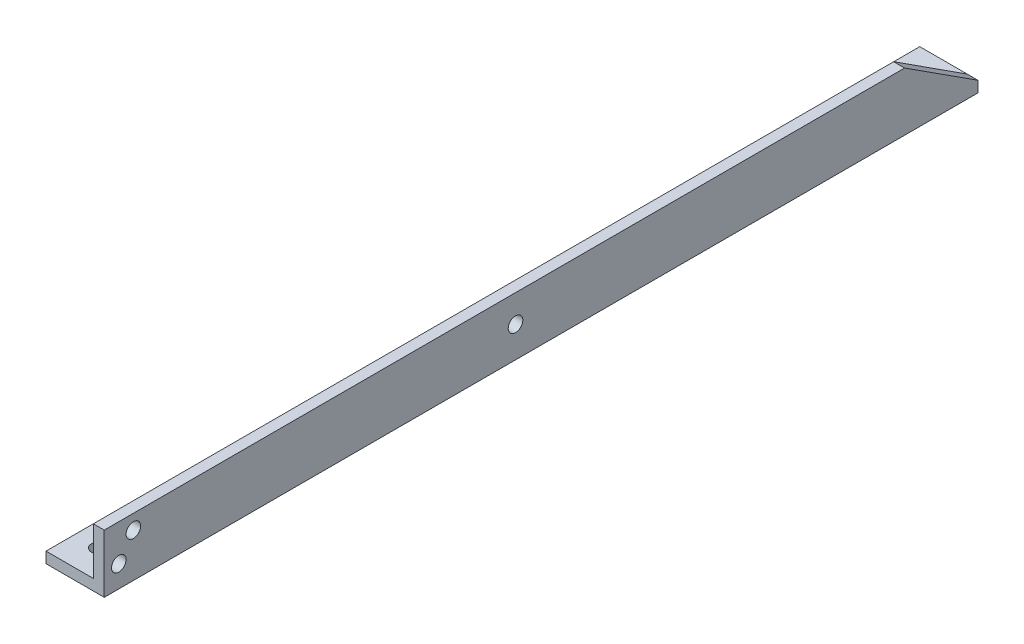
SolidWorks part; units mm, degrees
material "6061 Alloy"
ref_plane "Front Plane" through (0, 0, 0) normal (0, 0, 1) x (1, 0, 0)
ref_plane "Top Plane" through (0, 0, 0) normal (0, 1, 0) x (1, 0, 0)
ref_plane "Right Plane" through (0, 0, 0) normal (1, 0, 0) x (0, 0, -1)
sketch "Sketch1" plane through (0, 0, 0) normal (0, 0, 1) x (1, 0, 0)
  line L0 (0, 0) -> (0, -25.4)
  line L1 (0, -25.4) -> (-25.4, -25.4)
  line L2 (-25.4, -25.4) -> (-25.4, -20.6375)
  line L3 (-25.4, -20.6375) -> (-4.7625, -20.6375)
  line L4 (-4.7625, -20.6375) -> (-4.7625, 0)
  line L5 (-4.7625, 0) -> (0, 0)
  dimension "D1" = 4.7625
  dimension "D2" = 4.7625
  dimension "D3" = 25.4
  dimension "D4" = 25.4
extrude "Boss-Extrude1" add sketch "Sketch1" along normal blind 381
sketch "Sketch9" plane through (-4.7625, 0, 0) normal (-1, 0, 0) x (0, 0, 1)
  line L0 (0, -20.6375) -> (32.0266, 0)
  line L1 (381, 0) -> (0, 0) construction
  dimension "D1" = 38.1
extrude "Cut-Extrude2" cut sketch "Sketch9" against normal through all and the other way through all
sketch "Sketch10" plane through (-4.7625, 0, 0) normal (-1, 0, 0) x (0, 0, 1)
  line L0 (381, 0) -> (32.0266, 0) construction
  line L1 (381, 0) -> (381, -20.6375) construction
  circle A0 centre (374.65, -15.875) radius 3.175
  circle A1 centre (368.3, -6.35) radius 3.175
  dimension "D1" = 6.35
  dimension "D2" = 6.35
  dimension "D3" = 15.875
  dimension "D4" = 6.35
  dimension "D5" = 6.35
  dimension "D6" = 12.7
extrude "Cut-Extrude3" cut sketch "Sketch10" against normal up to next
sketch "Sketch11" plane through (0, 0, 0) normal (1, 0, 0) x (0, 0, -1)
  circle A0 centre (-201.6672, -11.9296) radius 3.175 construction
  circle A1 centre (-201.6672, -11.9296) radius 3.175
extrude "Cut-Extrude4" cut sketch "Sketch11" against normal up to next
sketch "Sketch12" plane through (0, -20.6375, 0) normal (0, 1, 0) x (1, 0, 0)
  line L0 (-25.4, -381) -> (-25.4, 0) construction
  line L1 (-4.7625, -381) -> (-25.4, -381) construction
  circle A0 centre (-15.0812, -368.3) radius 3.175
  dimension "D1" = 6.35
  dimension "D2" = 10.3187
  dimension "D3" = 12.7
extrude "Cut-Extrude5" cut sketch "Sketch12" against normal up to next
